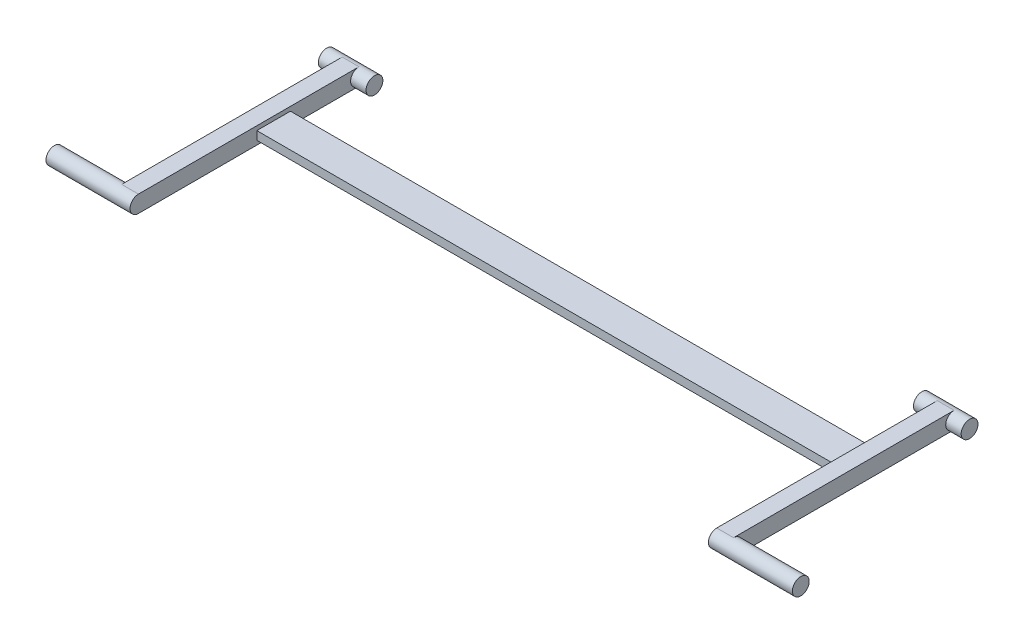
SolidWorks part; units mm, degrees
material "Alumina"
ref_plane "Front Plane" through (0, 0, 0) normal (0, 0, 1) x (1, 0, 0)
ref_plane "Top Plane" through (0, 0, 0) normal (0, 1, 0) x (1, 0, 0)
ref_plane "Right Plane" through (0, 0, 0) normal (1, 0, 0) x (0, 0, -1)
sketch "Sketch1" plane through (0, 0, 0) normal (0, 1, 0) x (1, 0, 0)
  line L1 (-109.22, 6.35) -> (109.22, 6.35)
  line L2 (-109.22, 6.35) -> (-109.22, -6.35)
  line L3 (-109.22, -6.35) -> (109.22, -6.35)
  line L4 (109.22, 6.35) -> (109.22, -6.35)
  line L5 (-109.22, 6.35) -> (109.22, -6.35) construction
  line L6 (-109.22, -6.35) -> (109.22, 6.35) construction
  point P0 (0, 0)
  dimension "D1" = 218.44
  dimension "D2" = 12.7
extrude "Boss-Extrude1" add sketch "Sketch1" along normal mid plane 3.175
sketch "Sketch2" plane through (109.22, 0, 0) normal (1, 0, 0) x (0, 0, -1)
  line L4 (-6.35, 3.175) -> (-51.054, 3.175)
  line L5 (-51.054, -3.175) -> (-6.35, -3.175)
  line L6 (-6.35, 1.5875) -> (6.35, 1.5875) construction
  line L7 (-6.35, 3.175) -> (32.258, 3.175)
  line L9 (32.258, -3.175) -> (-6.35, -3.175)
  arc A0 (32.258, 3.175) -> (32.258, -3.175) centre (32.258, 0) cw
  arc A1 (-51.054, 3.175) -> (-51.054, -3.175) centre (-51.054, 0) ccw
  dimension "D1" = 38.608
  dimension "D2" = 44.704
  dimension "D3" = 1.5875
  dimension "D4" = 6.35
extrude "Boss-Extrude3" add sketch "Sketch2" along normal blind 6.35
sketch "Sketch3" plane through (115.57, 0, 0) normal (1, 0, 0) x (0, 0, -1)
  line L0 (-54.229, 0) -> (-51.054, 0) construction
  arc A0 (-51.054, 3.175) -> (-51.054, -3.175) centre (-51.054, 0) ccw construction
  circle A1 centre (-51.054, 0) radius 3.175
  dimension "D1" = 6.35
extrude "Boss-Extrude4" add sketch "Sketch3" along normal blind 25.4
sketch "Sketch5" plane through (115.57, 0, 0) normal (1, 0, 0) x (0, 0, -1)
  circle A0 centre (32.258, 0) radius 3.175
  arc A1 (32.258, -3.175) -> (32.258, 3.175) centre (32.258, 0) ccw construction
extrude "Boss-Extrude5" add sketch "Sketch5" along normal blind 5.842
sketch "Sketch6" plane through (109.22, 0, 0) normal (-1, 0, 0) x (0, 0, 1)
  circle A0 centre (-32.258, 0) radius 3.175
  arc A1 (-32.258, 3.175) -> (-32.258, -3.175) centre (-32.258, 0) ccw construction
extrude "Boss-Extrude6" add sketch "Sketch6" along normal blind 5.842
mirror "Mirror1" about plane through (0, 0, 0) normal (1, 0, 0) of "Boss-Extrude5", "Boss-Extrude6", "Boss-Extrude3", "Boss-Extrude4"
